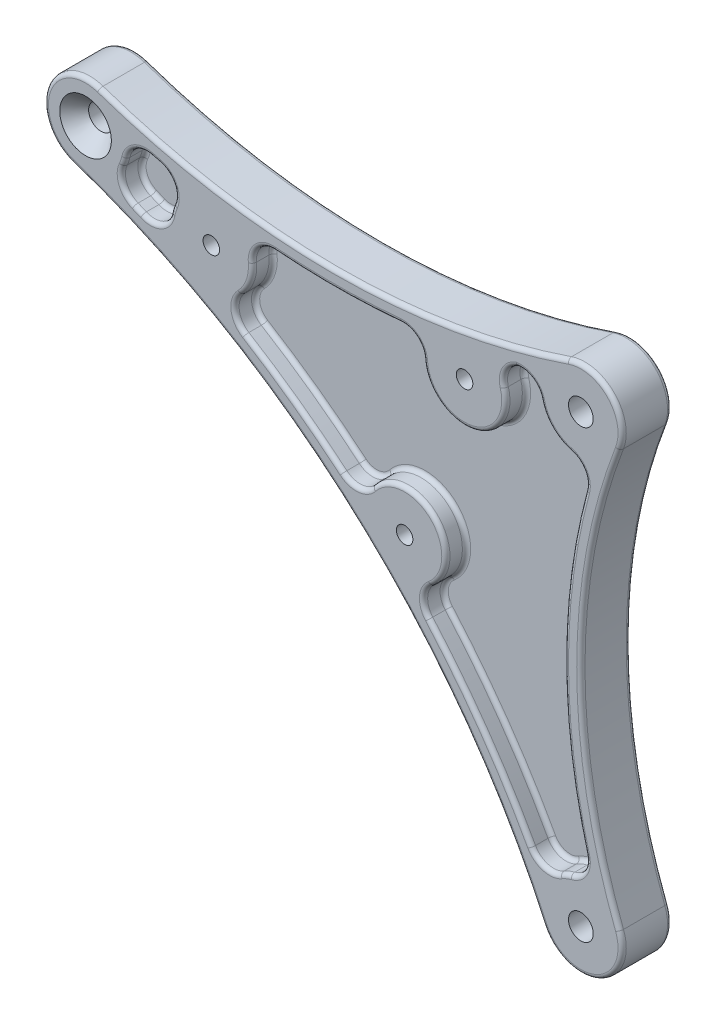
SolidWorks part; units mm, degrees
material "6063-O"
ref_plane "Front Plane" through (0, 0, 0) normal (0, 0, 1) x (1, 0, 0)
ref_plane "Top Plane" through (0, 0, 0) normal (0, 1, 0) x (1, 0, 0)
ref_plane "Right Plane" through (0, 0, 0) normal (1, 0, 0) x (0, 0, -1)
sketch "Sketch1" plane through (0, 0, 0) normal (0, 0, 1) x (1, 0, 0)
  line L0 (10.4775, 0) -> (-10.4775, 0) construction
  line L1 (0, -10.4775) -> (0, 10.4775) construction
  circle A0 centre (-190.5, 0) radius 4.7625
  circle A1 centre (0, 0) radius 4.7625
  circle A2 centre (0, -171.45) radius 4.7625
  arc A3 (-185.3514, 15.0169) -> (-195.5197, -15.0605) centre (-190.5, 0) ccw
  arc A4 (14.8223, -5.6847) -> (-5.1486, 15.0169) centre (0, 0) ccw
  arc A5 (-14.4504, -178.0229) -> (14.8223, -165.7653) centre (0, -171.45) ccw
  arc A6 (-185.3514, 15.0169) -> (-5.1486, 15.0169) centre (-95.25, 277.8125) ccw
  arc A7 (14.8223, -5.6847) -> (14.8223, -165.7653) centre (223.52, -85.725) ccw
  arc A8 (-195.5197, -15.0605) -> (-14.4504, -178.0229) centre (-291.8973, -304.222) cw
  dimension "D1" = 9.525
  dimension "D4" = 31.75
  dimension "D5" = 304.8
  dimension "D2" = 190.5
  dimension "D3" = 171.45
extrude "Boss-Extrude1" add sketch "Sketch1" along normal mid plane 19.05
hole_wizard "CSK for 3/8 Flat Head Socket Cap Screw1" positions "Sketch2" profile "Sketch3" countersink size "3/8" standard "ANSI Inch" end condition through all
sketch "Sketch2" plane through (0, 0, 9.525) normal (0, 0, 1) x (1, 0, 0)
  point P0 (-190.5, 0)
sketch "Sketch3" plane through (-190.5, 0, 9.525) normal (1, 0, 0) x (0, -1, 0)
  line L0 (0, 0) -> (0, 19.05)
  line L1 (0, 19.05) -> (4.7625, 19.05)
  line L2 (4.7625, 19.05) -> (4.7625, 5.9315)
  line L3 (4.7625, 5.9315) -> (9.9187, 0)
  line L5 (9.9187, 0) -> (0, 0)
  line L6 (-4.7625, 5.9315) -> (-9.9187, 0) construction
  line L11 (0, -6.35) -> (0, 107.95) construction
  dimension "Thru Hole Dia." = 9.525
  dimension "Thru Hole Depth" = 19.05
  dimension "Near C'Sink Dia." = 19.8374
  dimension "Near C'Sink Angle" = 82
hole_wizard "CSK for 3/8 Flat Head Socket Cap Screw2" positions "Sketch4" profile "Sketch5" countersink size "3/8" standard "ANSI Inch" end condition through all
sketch "Sketch4" plane through (0, 0, -9.525) normal (0, 0, -1) x (-1, 0, 0)
  point P0 (0, -171.45)
sketch "Sketch5" plane through (0, -171.45, -9.525) normal (1, 0, 0) x (0, 1, 0)
  line L0 (0, 0) -> (0, 19.05)
  line L1 (0, 19.05) -> (4.7625, 19.05)
  line L2 (4.7625, 19.05) -> (4.7625, 5.9315)
  line L3 (4.7625, 5.9315) -> (9.9187, 0)
  line L5 (9.9187, 0) -> (0, 0)
  line L6 (-4.7625, 5.9315) -> (-9.9187, 0) construction
  line L11 (0, -6.35) -> (0, 107.95) construction
  dimension "Thru Hole Dia." = 9.525
  dimension "Thru Hole Depth" = 19.05
  dimension "Near C'Sink Dia." = 19.8374
  dimension "Near C'Sink Angle" = 82
sketch "Sketch6" plane through (0, 0, 9.525) normal (0, 0, 1) x (1, 0, 0)
  line L0 (-44.7298, -11.4971) -> (-67.7906, -74.8563) construction
  line L1 (10.4775, 0) -> (-10.4775, 0) construction
  line L3 (-190.5, 0) -> (-56.2602, -43.1767) construction
  arc A0 (-181.7256, -13.2297) -> (-175.5075, 5.2193) centre (-190.5, 0) ccw
  arc A1 (-14.9925, 5.2193) -> (4.7532, -15.1467) centre (0, 0) ccw
  arc A2 (4.7532, -156.3033) -> (-14.0777, -164.1128) centre (0, -171.45) ccw
  arc A3 (-14.4504, -178.0229) -> (14.8223, -165.7653) centre (0, -171.45) ccw construction
  arc A4 (14.8223, -5.6847) -> (-5.1486, 15.0169) centre (0, 0) ccw construction
  arc A5 (-185.3514, 15.0169) -> (-195.5197, -15.0605) centre (-190.5, 0) ccw construction
  arc A6 (-58.7187, -3.992) -> (-34.1123, 0.3048) centre (-44.7298, -11.4971) ccw
  arc A7 (-65.677, -90.5899) -> (-83.5691, -73.1081) centre (-67.7906, -74.8563) ccw
  arc A8 (-34.1123, 0.3048) -> (-14.9925, 5.2193) centre (-95.25, 277.8125) ccw
  arc A9 (-83.5691, -73.1081) -> (-142.2364, -31.4292) centre (-291.8973, -304.222) ccw
  arc A10 (-185.3514, 15.0169) -> (-5.1486, 15.0169) centre (-95.25, 277.8125) ccw construction
  arc A11 (-187.4108, 9.0101) -> (-3.0892, 9.0101) centre (-95.25, 277.8125) ccw
  arc A12 (-175.5075, 5.2193) -> (-148.9732, -1.2254) centre (-95.25, 277.8125) ccw
  arc A13 (-14.4504, -178.0229) -> (-195.5197, -15.0605) centre (-291.8973, -304.222) ccw construction
  arc A14 (-8.6702, -175.3937) -> (-193.5118, -9.0363) centre (-291.8973, -304.222) ccw
  arc A15 (-14.0777, -164.1128) -> (-65.677, -90.5899) centre (-291.8973, -304.222) ccw
  arc A16 (-148.9732, -1.2254) -> (-155.0626, -24.7751) centre (-142.1399, -15.5545) ccw
  arc A17 (8.8934, -3.4108) -> (8.8934, -168.0392) centre (223.52, -85.725) ccw
  arc A18 (4.7532, -15.1467) -> (4.7532, -156.3033) centre (223.52, -85.725) ccw
  arc A19 (-131.1807, -4.0692) -> (-58.7187, -3.992) centre (-95.25, 277.8125) ccw
  arc A20 (-155.0626, -24.7751) -> (-181.7256, -13.2297) centre (-291.8973, -304.222) ccw
  arc A21 (-142.2364, -31.4292) -> (-131.1807, -4.0692) centre (-142.1399, -15.5545) ccw
  point P50 (0, 0)
  dimension "D4" = 70
  dimension "D5" = 38.1
  dimension "D6" = 50.8
  dimension "D1" = 6.35
  dimension "D2" = 6.35
  dimension "D3" = 6.35
extrude "Cut-Extrude1" cut sketch "Sketch6" against normal blind 7.9375
sketch "Sketch7" plane through (0, 0, -9.525) normal (0, 0, -1) x (-1, 0, 0)
  arc A4 (148.9732, -1.2254) -> (175.5075, 5.2193) centre (95.25, 277.8125) ccw
  arc A5 (175.5075, 5.2193) -> (181.7256, -13.2297) centre (190.5, 0) ccw
  arc A6 (-4.7532, -156.3033) -> (-4.7532, -15.1467) centre (-223.52, -85.725) ccw
  arc A7 (-4.7532, -15.1467) -> (14.9925, 5.2193) centre (0, 0) ccw
  arc A8 (58.7187, -3.992) -> (131.1807, -4.0692) centre (95.25, 277.8125) ccw
  arc A9 (58.7187, -3.992) -> (131.1807, -4.0692) centre (95.25, 277.8125) ccw
  arc A10 (65.677, -90.5899) -> (14.0777, -164.1128) centre (291.8973, -304.222) ccw
  arc A11 (14.0777, -164.1128) -> (-4.7532, -156.3033) centre (0, -171.45) ccw
  arc A12 (-4.7532, -156.3033) -> (-4.7532, -15.1467) centre (-223.52, -85.725) ccw
  arc A13 (-4.7532, -15.1467) -> (14.9925, 5.2193) centre (0, 0) ccw
  arc A16 (65.677, -90.5899) -> (14.0777, -164.1128) centre (291.8973, -304.222) ccw
  arc A17 (14.0777, -164.1128) -> (-4.7532, -156.3033) centre (0, -171.45) ccw
  arc A18 (181.7256, -13.2297) -> (155.0626, -24.7751) centre (291.8973, -304.222) ccw
  arc A19 (155.0626, -24.7751) -> (148.9732, -1.2254) centre (142.1399, -15.5545) ccw
  arc A20 (148.9732, -1.2254) -> (175.5075, 5.2193) centre (95.25, 277.8125) ccw
  arc A21 (175.5075, 5.2193) -> (181.7256, -13.2297) centre (190.5, 0) ccw
  arc A22 (14.9925, 5.2193) -> (34.1123, 0.3048) centre (95.25, 277.8125) ccw
  arc A23 (14.9925, 5.2193) -> (34.1123, 0.3048) centre (95.25, 277.8125) ccw
  arc A24 (34.1123, 0.3048) -> (58.7187, -3.992) centre (44.7298, -11.4971) ccw
  arc A25 (34.1123, 0.3048) -> (58.7187, -3.992) centre (44.7298, -11.4971) ccw
  arc A26 (142.2364, -31.4292) -> (83.5691, -73.1081) centre (291.8973, -304.222) ccw
  arc A27 (142.2364, -31.4292) -> (83.5691, -73.1081) centre (291.8973, -304.222) ccw
  arc A28 (83.5691, -73.1081) -> (65.677, -90.5899) centre (67.7906, -74.8563) ccw
  arc A29 (83.5691, -73.1081) -> (65.677, -90.5899) centre (67.7906, -74.8563) ccw
  arc A30 (131.1807, -4.0692) -> (142.2364, -31.4292) centre (142.1399, -15.5545) ccw
  arc A31 (131.1807, -4.0692) -> (142.2364, -31.4292) centre (142.1399, -15.5545) ccw
  arc A32 (181.7256, -13.2297) -> (155.0626, -24.7751) centre (291.8973, -304.222) ccw
  arc A33 (155.0626, -24.7751) -> (148.9732, -1.2254) centre (142.1399, -15.5545) ccw
  dimension "D1" = 0
  dimension "D2" = 0
extrude "Cut-Extrude2" cut sketch "Sketch7" against normal blind 7.9375
sketch "Sketch8" plane through (0, 0, 9.525) normal (0, 0, 1) x (1, 0, 0)
  circle A0 centre (-142.1399, -15.5545) radius 3.175
  circle A1 centre (-44.7298, -11.4971) radius 3.175
  circle A2 centre (-67.7906, -74.8563) radius 3.175
  dimension "D1" = 6.35
extrude "Cut-Extrude3" cut sketch "Sketch8" against normal through all
fillet "Fillet2" radius 7.9375 28 edges at (4.7532, -15.1467, -5.5563) (4.7532, -156.3033, -5.5563) (-14.0777, -164.1128, -5.5563) (4.7532, -15.1467, 5.5563) (-175.5075, 5.2193, 5.5563) (-14.0777, -164.1128, 5.5563) (4.7532, -156.3033, 5.5563) (-65.677, -90.5899, -5.5563) (-83.5691, -73.1081, -5.5563) (-142.2364, -31.4292, -5.5563) (-58.7187, -3.992, -5.5563) (-34.1123, 0.3048, -5.5563) (-14.9925, 5.2193, -5.5563) (-131.1807, -4.0692, -5.5563) (-181.7256, -13.2297, -5.5563) (-148.9732, -1.2254, -5.5563) (-155.0626, -24.7751, -5.5563) (-175.5075, 5.2193, -5.5563) (-14.9925, 5.2193, 5.5563) (-34.1123, 0.3048, 5.5563) (-131.1807, -4.0692, 5.5563) (-142.2364, -31.4292, 5.5563) (-83.5691, -73.1081, 5.5563) (-65.677, -90.5899, 5.5563) (-58.7187, -3.992, 5.5563) (-181.7256, -13.2297, 5.5563) (-155.0626, -24.7751, 5.5563) (-148.9732, -1.2254, 5.5563)
fillet "Fillet1" radius 1.5875 120 edges at (-95.25, 0, 9.525) (11.4251, 11.0219, 9.525) (0, -85.725, 9.525) (6.1316, -186.0931, 9.525) (-87.9969, -77.666, 9.525) (-95.25, 0, -9.525) (11.4251, 11.0219, -9.525) (0, -85.725, -9.525) (6.1316, -186.0931, -9.525) (-87.9969, -77.666, -9.525) (-6.35, -85.725, -1.5875) (-11.3742, -11.0744, -1.5875) (-37.2103, -125.4796, -1.5875) (-6.039, -156.7685, -1.5875) (-6.039, -156.7685, 1.5875) (-37.2103, -125.4796, 1.5875) (-175.4525, -5.0585, 1.5875) (-163.7215, 2.0228, 1.5875) (-11.3742, -11.0744, 1.5875) (-6.35, -85.725, 1.5875) (-205.5388, 5.0842, 9.525) (-205.5388, 5.0842, -9.525) (-14.1655, -158.564, -1.5875) (0.9735, -152.37, -1.5875) (0.9735, -19.08, -1.5875) (0.9735, -152.37, 1.5875) (-14.1655, -158.564, 1.5875) (-171.4215, 1.5021, 1.5875) (0.9735, -19.08, 1.5875) (-37.2103, -125.4796, -9.525) (-14.1655, -158.564, -9.525) (-6.039, -156.7685, -9.525) (0.9735, -152.37, -9.525) (-6.35, -85.725, -9.525) (0.9735, -19.08, -9.525) (0.9735, -19.08, 9.525) (-6.35, -85.725, 9.525) (0.9735, -152.37, 9.525) (-6.039, -156.7685, 9.525) (-14.1655, -158.564, 9.525) (-37.2103, -125.4796, 9.525) (-175.4525, -5.0585, 9.525) (-171.4215, 1.5021, 9.525) (-163.7215, 2.0228, 9.525) (-11.3742, -11.0744, -9.525) (-11.3742, -11.0744, 9.525) (-41.999, -27.1355, -1.5875) (-93.5018, -6.3446, -1.5875) (-127.1784, -20.862, -1.5875) (-109.9034, -51.8483, -1.5875) (-56.6962, -63.5015, -1.5875) (-56.6962, -63.5015, 1.5875) (-109.9034, -51.8483, 1.5875) (-127.1784, -20.862, 1.5875) (-93.5018, -6.3446, 1.5875) (-41.999, -27.1355, 1.5875) (-18.7872, 1.3149, -9.525) (-28.9052, -1.2858, -9.525) (-41.999, -27.1355, -9.525) (-63.3369, -7.0227, -9.525) (-93.5018, -6.3446, -9.525) (-124.076, -7.7892, -9.525) (-127.1784, -20.862, -9.525) (-132.9849, -33.1738, -9.525) (-109.9034, -51.8483, -9.525) (-85.658, -67.9667, -9.525) (-56.6962, -63.5015, -9.525) (-60.4885, -92.5591, -9.525) (-60.4885, -92.5591, 9.525) (-56.6962, -63.5015, 9.525) (-85.658, -67.9667, 9.525) (-109.9034, -51.8483, 9.525) (-132.9849, -33.1738, 9.525) (-127.1784, -20.862, 9.525) (-124.076, -7.7892, 9.525) (-93.5018, -6.3446, 9.525) (-63.3369, -7.0227, 9.525) (-41.999, -27.1355, 9.525) (-28.9052, -1.2858, 9.525) (-18.7872, 1.3149, 9.525) (-18.7872, 1.3149, -1.5875) (-28.9052, -1.2858, -1.5875) (-63.3369, -7.0227, -1.5875) (-124.076, -7.7892, -1.5875) (-132.9849, -33.1738, -1.5875) (-85.658, -67.9667, -1.5875) (-60.4885, -92.5591, -1.5875) (-60.4885, -92.5591, 1.5875) (-85.658, -67.9667, 1.5875) (-132.9849, -33.1738, 1.5875) (-124.076, -7.7892, 1.5875) (-63.3369, -7.0227, 1.5875) (-28.9052, -1.2858, 1.5875) (-18.7872, 1.3149, 1.5875) (-170.2828, -17.8233, 9.525) (-161.8165, -18.2163, 9.525) (-157.3238, -10.9213, 9.525) (-156.8834, -2.5455, 9.525) (-156.8834, -2.5455, 1.5875) (-157.3238, -10.9213, 1.5875) (-161.8165, -18.2163, 1.5875) (-170.2828, -17.8233, 1.5875) (-163.7215, 2.0228, -9.525) (-156.8834, -2.5455, -9.525) (-157.3238, -10.9213, -9.525) (-161.8165, -18.2163, -9.525) (-170.2828, -17.8233, -9.525) (-176.1982, -12.7345, -9.525) (-175.4525, -5.0585, -9.525) (-175.4525, -5.0585, -1.5875) (-176.1982, -12.7345, -1.5875) (-170.2828, -17.8233, -1.5875) (-161.8165, -18.2163, -1.5875) (-157.3238, -10.9213, -1.5875) (-156.8834, -2.5455, -1.5875) (-163.7215, 2.0228, -1.5875) (-176.1982, -12.7345, 9.525) (-176.1982, -12.7345, 1.5875) (-171.4215, 1.5021, -9.525) (-171.4215, 1.5021, -1.5875)
